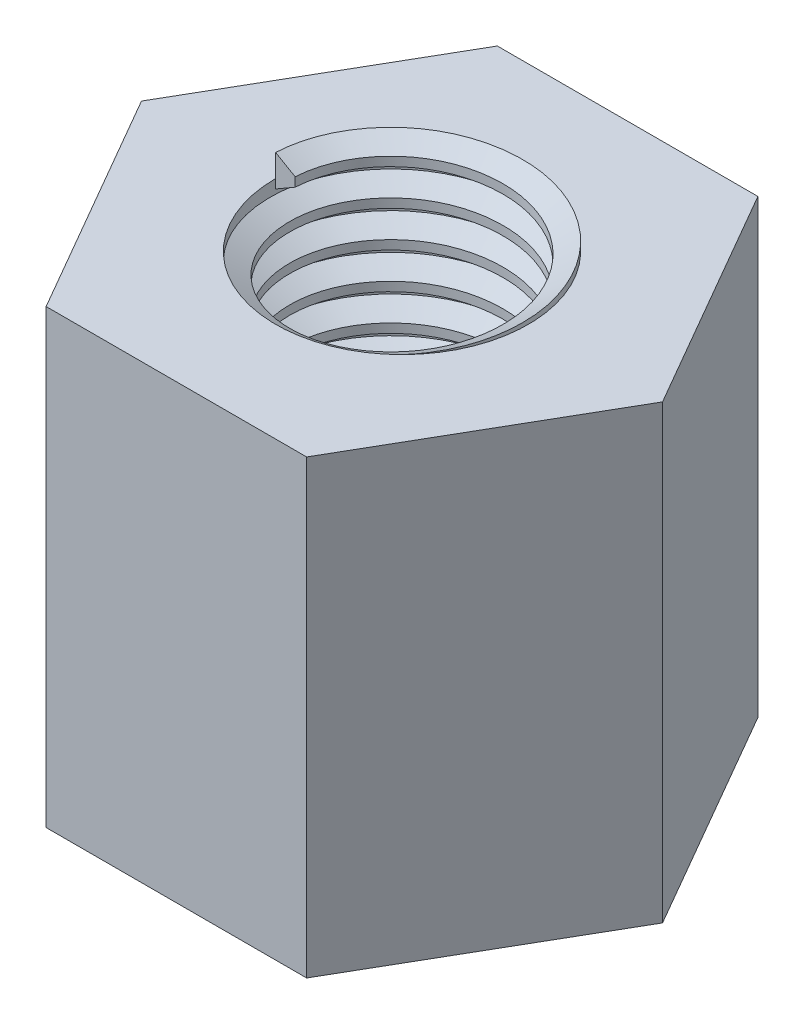
SolidWorks part; units mm, degrees
ref_plane "Front Plane" through (0, 0, 0) normal (0, 0, 1) x (1, 0, 0)
ref_plane "Top Plane" through (0, 0, 0) normal (0, 1, 0) x (1, 0, 0)
ref_plane "Right Plane" through (0, 0, 0) normal (1, 0, 0) x (0, 0, -1)
sketch "Sketch1" plane through (0, 0, 0) normal (0, 1, 0) x (1, 0, 0)
  line L1 (5.7735, 0) -> (2.8868, 5)
  line L2 (2.8868, 5) -> (-2.8868, 5)
  line L3 (-2.8868, 5) -> (-5.7735, 0)
  line L4 (-5.7735, 0) -> (-2.8868, -5)
  line L5 (-2.8868, -5) -> (2.8868, -5)
  line L6 (2.8868, -5) -> (5.7735, 0)
  circle A0 centre (0, 0) radius 2.8
  circle A1 centre (0, 0) radius 5 construction
  dimension "D1" = 5.6
  dimension "D2" = 10
extrude "Boss-Extrude1" add sketch "Sketch1" along normal blind 10
thread "Thread1" pitch 0.8 start angle 0, offset 0.5, length 0, pitch 0.8, diameter 5.6
ref_plane "Plane1" through (-2.8, 10.5, 0) normal (0, 0, 1) x (-1, 0, 0)
sketch "Thread Profile1" plane through (-2.8, 10.5, 0) normal (0, 0, 1) x (-1, 0, 0)
  line L0 (0, 0) -> (0, 0.8) construction
  line L11 (0, 0) -> (0, 0.7)
  line L12 (0, 0.7) -> (-0.433, 0.45)
  line L13 (-0.433, 0.45) -> (-0.433, 0.25)
  line L15 (-0.433, 0.25) -> (0, 0)
  line L17 (-0.433, 0.35) -> (0, 0.35) construction
  point P2 (0, 0)
  dimension "Pitch" = 0.8
  dimension "Profile_Angle" = 60
  dimension "Profile_Land" = 0.2
  dimension "Profile_Height" = 0.433
